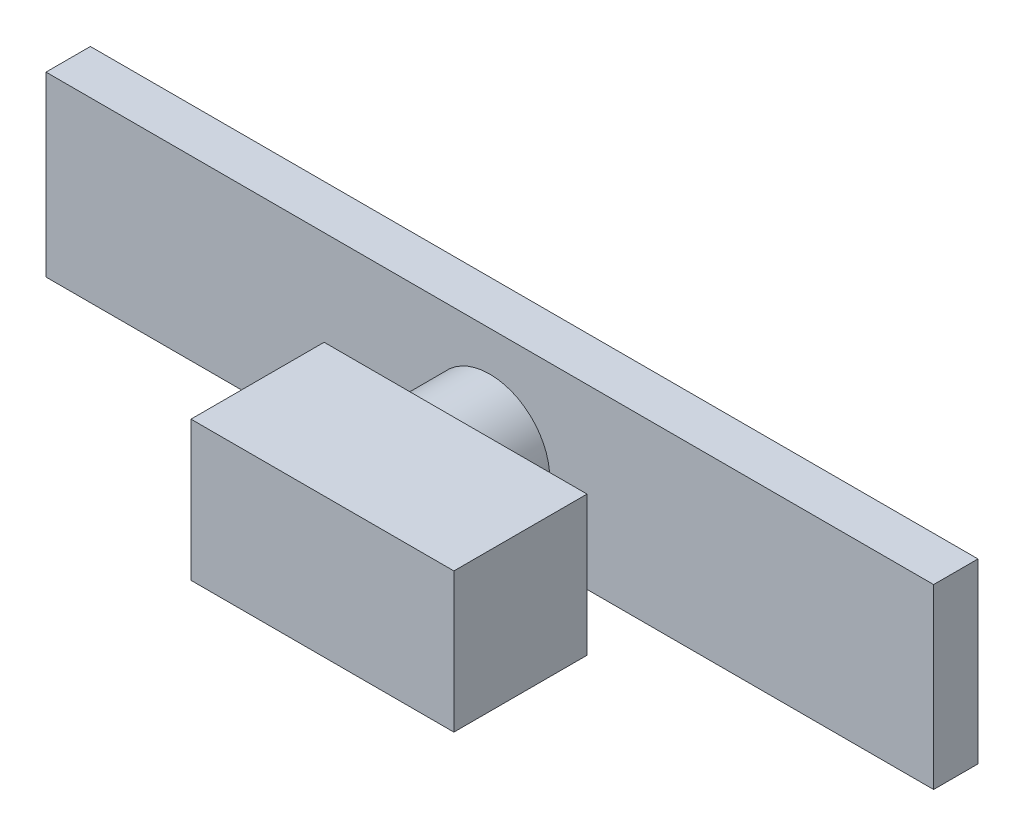
SolidWorks part; units mm, degrees
ref_plane "Front Plane" through (0, 0, 0) normal (0, 0, 1) x (1, 0, 0)
ref_plane "Top Plane" through (0, 0, 0) normal (0, 1, 0) x (1, 0, 0)
ref_plane "Right Plane" through (0, 0, 0) normal (1, 0, 0) x (0, 0, -1)
sketch "Sketch2" plane through (0, 0, 0) normal (0, 0, 1) x (1, 0, 0)
  line L1 (-47.8692, 21.2481) -> (206.1308, 21.2481)
  line L2 (-47.8692, 21.2481) -> (-47.8692, 8.5481)
  line L3 (-47.8692, 8.5481) -> (206.1308, 8.5481)
  line L4 (206.1308, 21.2481) -> (206.1308, 8.5481)
  dimension "D1" = 12.7
  dimension "D2" = 254
extrude "Boss-Extrude1" add sketch "Sketch2" along normal blind 50.8
sketch "Sketch3" plane through (0, 21.2481, 0) normal (0, 1, 0) x (1, 0, 0)
  circle A0 centre (79.1308, -28.4831) radius 17.1408
extrude "Boss-Extrude2" add sketch "Sketch3" along normal blind 19.05
sketch "Sketch4" plane through (0, 40.2981, 0) normal (0, 1, 0) x (1, 0, 0)
  line L1 (50.7675, -8.111) -> (126.0034, -8.111)
  line L2 (50.7675, -8.111) -> (50.7675, -48.0661)
  line L3 (50.7675, -48.0661) -> (126.0034, -48.0661)
  line L4 (126.0034, -8.111) -> (126.0034, -48.0661)
extrude "Boss-Extrude3" add sketch "Sketch4" along normal blind 38.1
scale "Scale2" scale about centroid uniform scaling yes scale factor 0.06
move or copy body "rotate" bodies to move or copy 105 copy no rotation origin (0, 33.6669, 26.5501) rotation axis (1, 0, 0) rotation angle 90
scale "Scale5" scale about centroid uniform scaling yes scale factor 0.25
move or copy body "-4 x" bodies to move or copy 111 copy no translate (-101.6, 0, 0)
move or copy body "-2 y" bodies to move or copy 117 copy no translate (0, -50.8, 0)
scale "Scale6" bodies to scale 121 scale about centroid uniform scaling yes scale factor 0.25
move or copy body "-2.1z" bodies to move or copy 122 copy no translate (0, 0, -25.4)
